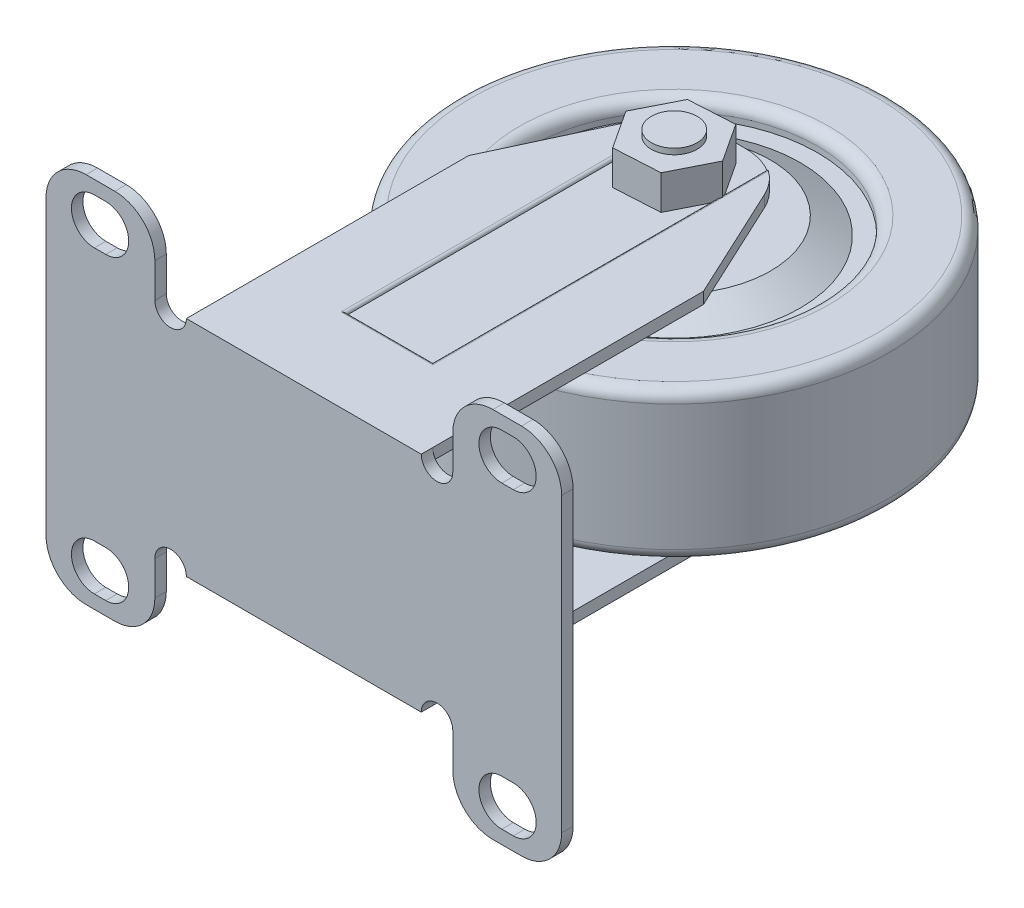
SolidWorks part; units mm, degrees
ref_plane "前视基准面" through (0, 0, 0) normal (0, 0, 1) x (1, 0, 0)
ref_plane "上视基准面" through (0, 0, 0) normal (0, 1, 0) x (1, 0, 0)
ref_plane "右视基准面" through (0, 0, 0) normal (1, 0, 0) x (0, 0, -1)
sketch "草图1" plane through (0, 0, 0) normal (0, 0, 1) x (1, 0, 0)
  line L1 (-45, 32.5) -> (45, 32.5)
  line L2 (-45, 32.5) -> (-45, -32.5)
  line L3 (-45, -32.5) -> (45, -32.5)
  line L4 (45, 32.5) -> (45, -32.5)
  line L5 (-45, 32.5) -> (45, -32.5) construction
  line L6 (-45, -32.5) -> (45, 32.5) construction
  point P0 (0, 0)
  dimension "D1" = 90
  dimension "D2" = 65
extrude "凸台-拉伸1" add sketch "草图1" along normal blind 2
sketch "草图2" plane through (0, 0, 2) normal (0, 0, 1) x (1, 0, 0)
  line L0 (-26, 32.5) -> (26, 32.5)
  line L1 (-26, 32.5) -> (-26, 19.5)
  line L2 (26, 32.5) -> (26, 19.5)
  line L3 (-26, 19.5) -> (26, 19.5)
  line L4 (45, 32.5) -> (-45, 32.5) construction
  line L5 (-45, 32.5) -> (-45, -32.5) construction
  line L6 (45, -32.5) -> (45, 32.5) construction
  dimension "D1" = 19
  dimension "D2" = 13
  dimension "D3" = 19
extrude "切除-拉伸1" cut sketch "草图2" against normal through all
mirror "镜向1" about plane through (0, 0, 0) normal (0, 1, 0) of "切除-拉伸1"
sketch "草图3" plane through (0, 0, 2) normal (0, 0, 1) x (1, 0, 0)
  line L0 (-36.5622, 26.1597) -> (-34.5622, 26.1597) construction
  line L1 (-36.5622, 30.1597) -> (-34.5622, 30.1597)
  line L2 (-36.5622, 22.1597) -> (-34.5622, 22.1597)
  arc A0 (-36.5622, 30.1597) -> (-36.5622, 22.1597) centre (-36.5622, 26.1597) ccw
  arc A1 (-34.5622, 22.1597) -> (-34.5622, 30.1597) centre (-34.5622, 26.1597) ccw
  point P2 (-35.5622, 26.1597)
  dimension "D1" = 4
  dimension "D2" = 2
extrude "切除-拉伸2" cut sketch "草图3" against normal through all
mirror "镜向2" about plane through (0, 0, 0) normal (1, 0, 0) of "切除-拉伸2"
mirror "镜向3" about plane through (0, 0, 0) normal (0, 1, 0) of "镜向2", "切除-拉伸2"
fillet "圆角1" radius 7 8 edges at (45, -32.5, 1) (26, -32.5, 1) (-26, -32.5, 1) (-45, -32.5, 1) (45, 32.5, 1) (26, 32.5, 1) (-26, 32.5, 1) (-45, 32.5, 1)
sketch "草图4" plane through (0, 0, 0) normal (0, 0, -1) x (-1, 0, 0)
  line L0 (26, 19.5) -> (-26, 19.5) construction
  line L1 (-20.5, 19.5) -> (20.5, 19.5)
  line L2 (-20.5, 19.5) -> (-20.5, 17.5)
  line L3 (-20.5, 17.5) -> (20.5, 17.5)
  line L4 (20.5, 19.5) -> (20.5, 17.5)
  point P6 (0, 17.5)
  dimension "D1" = 41
  dimension "D2" = 2
extrude "凸台-拉伸2" add sketch "草图4" along normal blind 73
mirror "镜向4" about plane through (0, 0, 0) normal (0, 1, 0) of "凸台-拉伸2"
sketch "草图5" plane through (0, 19.5, 0) normal (0, 1, 0) x (1, 0, 0)
  line L0 (-20.5, 73) -> (20.5, 73) construction
  line L1 (-7.5, 73) -> (7.5, 73)
  line L2 (-7.5, 73) -> (-7.5, 13.0086)
  line L3 (-7.5, 13.0086) -> (7.5, 13.0086)
  line L4 (7.5, 73) -> (7.5, 13.0086)
  point P6 (0, 73)
  dimension "D1" = 15
extrude "切除-拉伸3" cut sketch "草图5" against normal blind 0.5
fillet "圆角2" radius 0.5 3 edges at (0, 19.5, -13.0086) (7.5, 19.5, -43.0043) (-7.5, 19.5, -43.0043)
mirror "镜向6" about plane through (0, 0, 0) normal (0, 1, 0) of "切除-拉伸3"
fillet "圆角3" radius 0.5 3 edges at (7.5, -19.5, -43.0043) (-7.5, -19.5, -43.0043) (0, -19.5, -13.0086)
chamfer "倒角4" distance 12 angle 65 1 edges at (-20.5, -18.5, -73) first distance on face at (0, -18.9009, -73)
chamfer "倒角5" distance 12 angle 65 1 edges at (20.5, -18.5, -73) first distance on face at (3, -18.9009, -73)
chamfer "倒角6" distance 12 angle 65 1 edges at (20.5, 18.5, -73) first distance on face at (0, 18.9009, -73)
chamfer "倒角7" distance 12 angle 65 1 edges at (-20.5, 18.5, -73) first distance on face at (-3, 18.9009, -73)
fillet "圆角4" radius 10 4 edges at (-8.5, 18.5, -73) (8.5, 18.5, -73) (8.5, -18.5, -73) (-8.5, -18.5, -73)
sketch "草图6" plane through (0, 19, 0) normal (0, 1, 0) x (1, 0, 0)
  line L1 (-4.3911, 69.3426) -> (-7.9868, 62.1963)
  line L2 (-7.9868, 62.1963) -> (-3.5957, 55.5091)
  line L3 (-3.5957, 55.5091) -> (4.3911, 55.9683)
  line L4 (4.3911, 55.9683) -> (7.9868, 63.1147)
  line L5 (7.9868, 63.1147) -> (3.5957, 69.8018)
  line L6 (3.5957, 69.8018) -> (-4.3911, 69.3426)
  circle A0 centre (0, 62.6555) radius 8 construction
  dimension "D1" = 16
extrude "凸台-拉伸3" add sketch "草图6" along normal blind 6
sketch "草图7" plane through (0, 25, 0) normal (0, 1, 0) x (1, 0, 0)
  circle A0 centre (0, 62.6555) radius 4
  dimension "D1" = 8
extrude "凸台-拉伸4" add sketch "草图7" along normal blind 1 and the other way blind 41
mirror "镜向7" about plane through (0, 0, 0) normal (0, 1, 0) of "凸台-拉伸4", "凸台-拉伸3"
sketch "草图8" plane through (0, 0, 0) normal (0, 0, -1) x (-1, 0, 0)
  line L0 (-20.5, 19.5) -> (-26, 19.5) construction
  circle A0 centre (-23.25, 19.5) radius 2.75
extrude "切除-拉伸4" cut sketch "草图8" against normal through all
mirror "镜向8" about plane through (0, 0, 0) normal (0, 1, 0) of "切除-拉伸4"
mirror "镜向9" about plane through (0, 0, 0) normal (1, 0, 0) of "切除-拉伸4", "镜向8"
sketch "草图10" plane through (0, 0, 0) normal (0, 1, 0) x (1, 0, 0)
  circle A0 centre (0, 62.6555) radius 37.5
  dimension "D1" = 75
extrude "凸台-拉伸7" add sketch "草图10" along normal blind 13 and the other way blind 13
fillet "圆角5" radius 2 2 edges at (0, -13, -25.1555) (0, 13, -25.1555)
sketch "草图11" plane through (0, 13, 0) normal (0, 1, 0) x (1, 0, 0)
  circle A0 centre (0, 62.6555) radius 25
  circle A1 centre (0, 62.6555) radius 22
  dimension "D1" = 50
  dimension "D2" = 44
extrude "切除-拉伸5" cut sketch "草图11" against normal blind 3
fillet "圆角6" radius 2 1 edges at (0, 13, -37.6555)
mirror "镜向10" about plane through (0, 0, 0) normal (0, 1, 0) of "切除-拉伸5"
fillet "圆角7" radius 2 1 edges at (0, -13, -37.6555)
chamfer "倒角8" distance 3 angle 60 1 edges at (0, 13, -40.6555) first distance on face at (0, 10, -40.6555)
chamfer "倒角9" distance 3 angle 60 1 edges at (0, -13, -40.6555) first distance on face at (0, -10, -40.6555)
